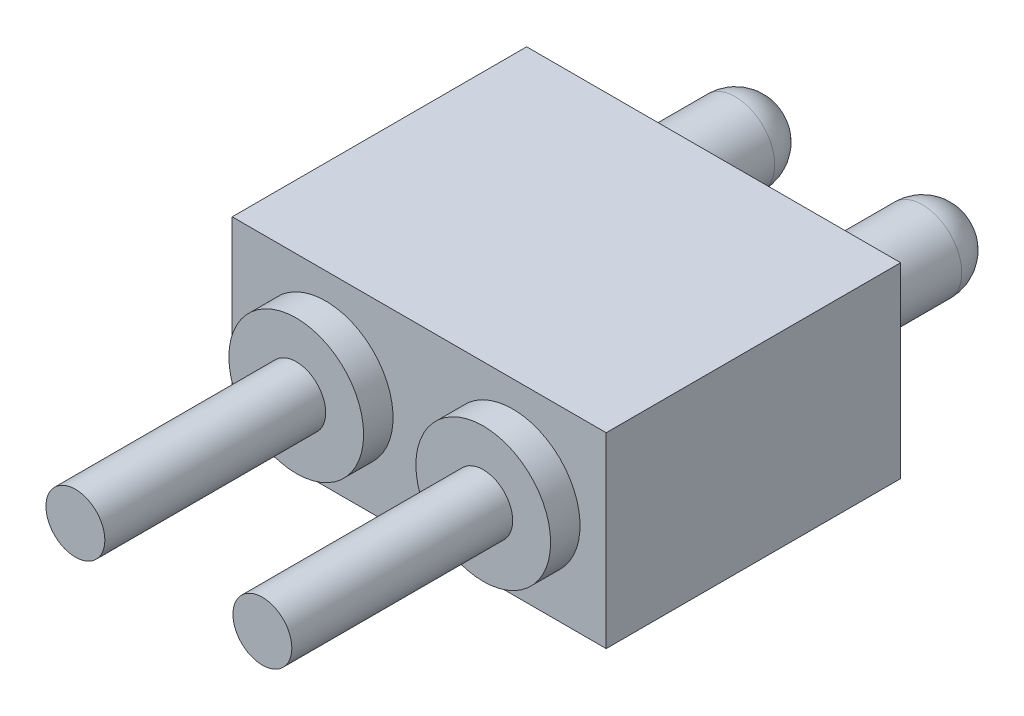
SolidWorks part; units mm, degrees
material "ABS"
ref_plane "Plan de face" through (0, 0, 0) normal (0, 0, 1) x (1, 0, 0)
ref_plane "Plan de dessus" through (0, 0, 0) normal (0, 1, 0) x (1, 0, 0)
ref_plane "Plan de droite" through (0, 0, 0) normal (1, 0, 0) x (0, 0, -1)
sketch "Esquisse1" plane through (0, 0, 0) normal (0, 0, 1) x (1, 0, 0)
  line L1 (0, 0) -> (5.08, 0)
  line L2 (0, 0) -> (0, 2.54)
  line L3 (0, 2.54) -> (5.08, 2.54)
  line L4 (5.08, 0) -> (5.08, 2.54)
  dimension "D1" = 2.54
  dimension "D2" = 5.08
extrude "Extrusion1" add sketch "Esquisse1" along normal blind 4
sketch "Esquisse2" plane through (0, 0, 4) normal (0, 0, 1) x (1, 0, 0)
  line L0 (2.54, 2.9529) -> (2.54, -0.4913) construction
  line L1 (1.27, 2.9529) -> (1.27, -0.4913) construction
  line L2 (3.81, 2.9529) -> (3.81, -0.4913) construction
  line L8 (5.08, 1.27) -> (0, 1.27) construction
  circle A0 centre (3.81, 1.27) radius 0.915
  circle A1 centre (1.27, 1.27) radius 0.915
  dimension "D1" = 1.27
  dimension "D2" = 1.27
extrude "Extrusion2" add sketch "Esquisse2" along normal blind 0.4
sketch "Esquisse3" plane through (0, 0, 0) normal (0, 0, -1) x (-1, 0, 0)
  circle A0 centre (-3.81, 1.27) radius 0.535
  circle A1 centre (-1.27, 1.27) radius 0.535
extrude "Extrusion3" add sketch "Esquisse3" along normal blind 1.565
dome "Dôme1" faces to dome 1 distance 0.535 reverse direction no elliptical dome no face at (3.275, 1.27, -1.565) parameters "D1"=0.535
dome "Dôme2" faces to dome 1 distance 0.535 reverse direction no elliptical dome no face at (0.735, 1.27, -1.565) parameters "D1"=0.535
sketch "Esquisse4" plane through (0, 0, 4.4) normal (0, 0, 1) x (1, 0, 0)
  circle A0 centre (3.81, 1.27) radius 0.4
  circle A1 centre (1.27, 1.27) radius 0.4
extrude "Extrusion4" add sketch "Esquisse4" along normal blind 3
